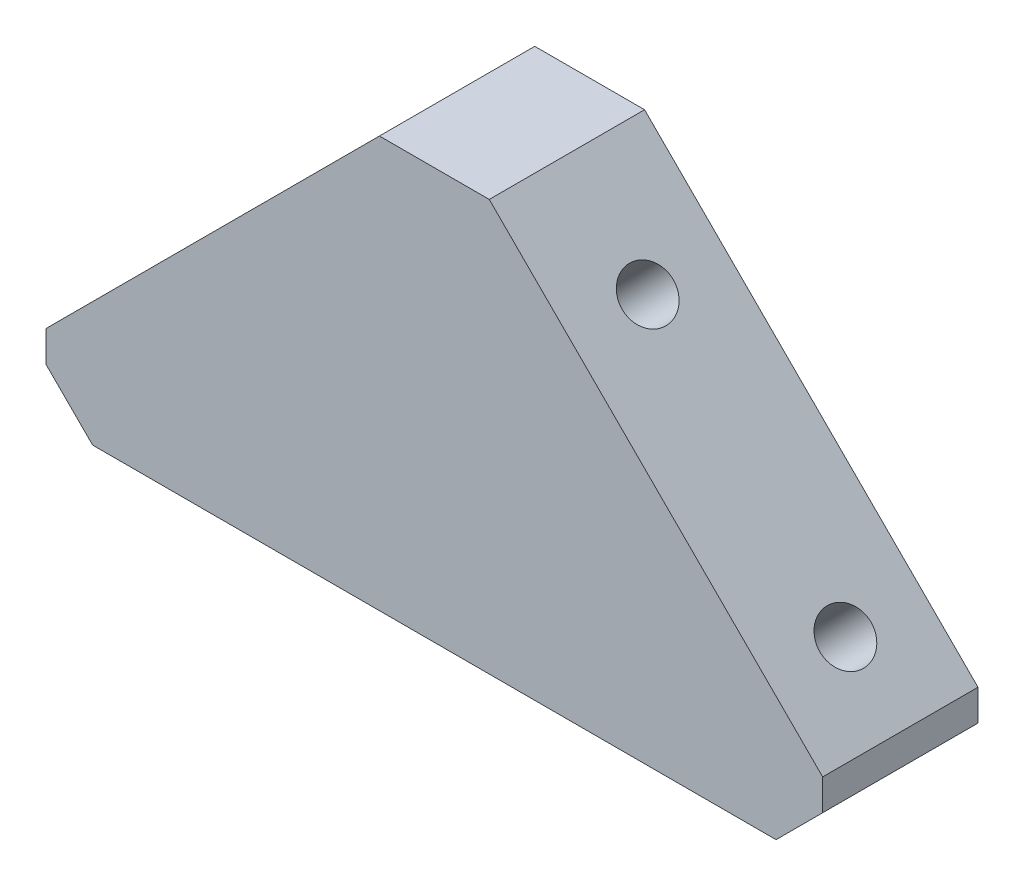
SolidWorks part; units mm, degrees
ref_plane "Front" through (0, 0, 0) normal (0, 0, 1) x (1, 0, 0)
ref_plane "Top" through (0, 0, 0) normal (0, 1, 0) x (1, 0, 0)
ref_plane "Right" through (0, 0, 0) normal (1, 0, 0) x (0, 0, -1)
sketch "Esquisse1" plane through (0, 0, 0) normal (0, 0, 1) x (1, 0, 0)
  line L0 (-25, 0) -> (25, 0)
  line L1 (25, 0) -> (25, 5)
  line L2 (25, 5) -> (0, 30)
  line L3 (0, 30) -> (0, 0) construction
  line L4 (-25, 5) -> (0, 30)
  line L5 (-25, 0) -> (-25, 5)
  point P5 (25, 2.5)
  dimension "D1" = 50
  dimension "D2" = 45
  dimension "D3" = 5
extrude "Boss.-Extru.1" add sketch "Esquisse1" along normal blind 10
sketch "Esquisse2" plane through (15, 15, 0) normal (0.7071, 0.7071, 0) x (0, 0, -1)
  line L0 (-5, -14.1421) -> (-5, 21.2132) construction
  line L1 (-10, -14.1421) -> (0, -14.1421) construction
  line L2 (-10, 21.2132) -> (0, 21.2132) construction
  circle A0 centre (-5, 8.8579) radius 1.65
  circle A1 centre (-5, -9.1421) radius 1.65
  dimension "D1" = 18
  dimension "D2" = 3.3
  dimension "D3" = 5
extrude "Enlèv. mat.-Extru.1" cut sketch "Esquisse2" against normal blind 8
sketch "Esquisse3" plane through (-15, 15, 0) normal (-0.7071, 0.7071, 0) x (0, 0, 1)
  line L0 (5, -14.1421) -> (5, 21.2132) construction
  line L1 (10, -14.1421) -> (0, -14.1421) construction
  line L2 (10, 21.2132) -> (0, 21.2132) construction
  circle A0 centre (5, 9.8579) radius 1.65
  circle A1 centre (5, -8.1421) radius 1.65
  dimension "D1" = 18
  dimension "D2" = 3.3
  dimension "D3" = 6
extrude "Enlèv. mat.-Extru.2" cut sketch "Esquisse3" against normal blind 8
chamfer "Chanfrein1" distance 5 angle 45 1 edges at (0, 30, 5)
sketch "Esquisse4" plane through (0, 0, 0) normal (0, -1, 0) x (1, 0, 0)
  line L0 (-25, 5) -> (25, 5) construction
  line L1 (-25, 10) -> (-25, 0) construction
  line L2 (25, 10) -> (25, 0) construction
  line L3 (0, 5) -> (0, 8.5239) construction
  circle A0 centre (0, 5) radius 1.65
  circle A1 centre (-16, 5) radius 1.65
  circle A2 centre (16, 5) radius 1.65
  dimension "D1" = 3.3
  dimension "D2" = 16
extrude "Enlèv. mat.-Extru.3" cut sketch "Esquisse4" against normal blind 10
chamfer "Chanfrein3" distance 3 angle 45 2 edges at (25, 0, 5) (-25, 0, 5)
sketch "Esquisse5" plane through (0, 0, 10) normal (0, 0, 1) x (1, 0, 0)
  line L0 (7.5, 5) -> (7.5, 15) construction
  line L1 (-22, 0) -> (22, 0) construction
  circle A0 centre (7.5, 15) radius 1.75
  circle A1 centre (7.5, 5) radius 1.75
  dimension "D1" = 3.5
  dimension "D2" = 10
  dimension "D3" = 5
  dimension "D4" = 7.5
extrude "Enlèv. mat.-Extru.4" [suppressed] cut sketch "Esquisse5" against normal through all
sketch "Esquisse6" [suppressed] plane through (0, 0, 0) normal (0, -1, 0) x (1, 0, 0)
  circle A0 centre (0, 5) radius 4.05
  dimension "D1" = 8.1
extrude "Enlèv. mat.-Extru.5" [suppressed] cut sketch "Esquisse6" against normal blind 20
